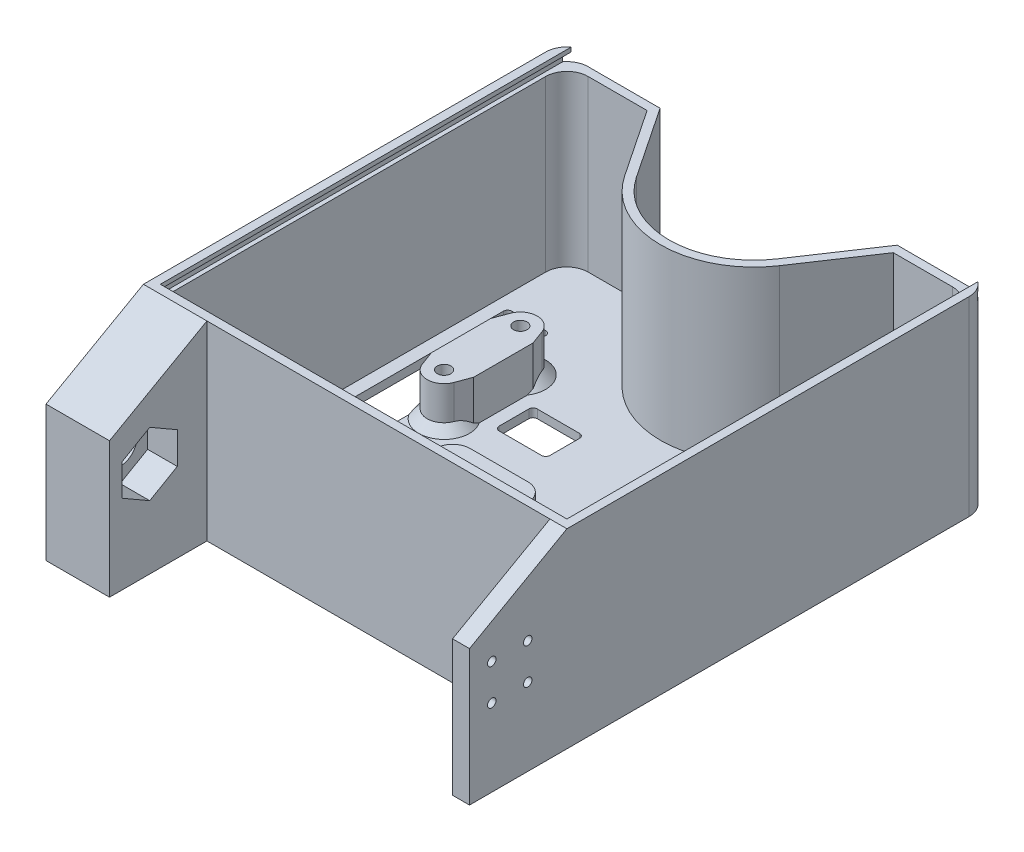
SolidWorks part; units mm, degrees
material "PVC hart"
ref_plane "Ebene vorne" through (0, 0, 0) normal (0, 0, 1) x (1, 0, 0)
ref_plane "Ebene oben" through (0, 0, 0) normal (0, 1, 0) x (1, 0, 0)
ref_plane "Ebene rechts" through (0, 0, 0) normal (1, 0, 0) x (0, 0, -1)
sketch "Grundplatte" plane through (0, 0, 0) normal (0, 1, 0) x (1, 0, 0)
  line L0 (0, 69.0751) -> (0, -94.5087) construction
  line L2 (-50, 50) -> (-50, -50)
  line L3 (-50, -50) -> (50, -50)
  line L4 (50, 50) -> (50, -50)
  line L5 (-50, 50) -> (50, -50) construction
  line L6 (-50, -50) -> (50, 50) construction
  line L7 (-50, 50) -> (-28, 50)
  line L8 (-28, 50) -> (-16.6199, 33)
  line L9 (28, 50) -> (16.6199, 33)
  line L10 (50, 50) -> (28, 50)
  arc A0 (-16.6199, 33) -> (16.6199, 33) centre (0, 44.1257) ccw
  point P0 (0, 0)
  dimension "D4" = 20
  dimension "D1" = 100
  dimension "D2" = 100
  dimension "D3" = 22
  dimension "D5" = 17
extrude "Aufsatz-Linear austragen1" add sketch "Grundplatte" along normal blind 45
shell "Wandung1" thickness 2 removed face at (0, 45, -19.6407)
sketch "Skizze1" plane through (0, 2, 0) normal (0, 1, 0) x (1, 0, 0)
  line L0 (0, 51.8201) -> (0, -55.3816) construction
  line L1 (-28, 50) -> (-50, 50) construction
  line L2 (-45, 31) -> (-35, 31)
  line L3 (-45, 31) -> (-45, -11)
  line L4 (-45, -11) -> (-35, -11)
  line L5 (-35, 31) -> (-35, -11)
  line L6 (-45, 31) -> (-35, -11) construction
  line L7 (-45, -11) -> (-35, 31) construction
  line L8 (50, 50) -> (28, 50) construction
  line L9 (35, 31) -> (45, 31)
  line L10 (35, 31) -> (35, -11)
  line L11 (35, -11) -> (45, -11)
  line L12 (45, 31) -> (45, -11)
  line L13 (35, 31) -> (45, -11) construction
  line L14 (35, -11) -> (45, 31) construction
  point P3 (-40, 10)
  point P10 (40, 10)
  dimension "D1" = 10
  dimension "D2" = 42
  dimension "D3" = 40
  dimension "D4" = 40
  dimension "D5" = 42
  dimension "D6" = 10
  dimension "D7" = 40
  dimension "D8" = 40
extrude "Schnitt-Linear austragen1" cut sketch "Skizze1" against normal up to surface (2 mm away) up to face at (0, 0, -19.6407)
sketch "Skizze2" plane through (0, 2, 0) normal (0, 1, 0) x (1, 0, 0)
  line L20 (-65.457, 10) -> (65.6069, 10) construction
  line L21 (0, 51.8201) -> (0, -54.6693) construction
  line L22 (-35, -11) -> (-35, 31) construction
  line L24 (-35, 16) -> (-35, 4)
  line L26 (-25, 16) -> (-25, 4)
  line L27 (-35, 16) -> (-25, 4) construction
  line L28 (-35, 4) -> (-25, 16) construction
  line L33 (35, 16) -> (35, 17)
  line L34 (33.7533, 20.3831) -> (35, 17)
  line L36 (-35, 16) -> (-35, 17)
  line L37 (-25, 16) -> (-25, 17)
  line L38 (-35, 4) -> (-35, 3)
  line L39 (-25, 4) -> (-25, 3)
  line L40 (-26.2467, 20.3831) -> (-25, 17)
  line L41 (-33.7533, 20.3831) -> (-35, 17)
  line L42 (-26.2467, -0.3831) -> (-25, 3)
  line L43 (-33.7533, -0.3831) -> (-35, 3)
  line L44 (26.2467, 20.3831) -> (25, 17)
  line L45 (25, 16) -> (25, 17)
  line L46 (25, 16) -> (25, 4)
  line L47 (25, 4) -> (25, 3)
  line L48 (26.2467, -0.3831) -> (25, 3)
  line L49 (33.7533, -0.3831) -> (35, 3)
  line L50 (35, 4) -> (35, 3)
  line L51 (35, 16) -> (35, 4)
  circle A4 centre (-30, 19) radius 1.6
  circle A5 centre (-30, 1) radius 1.6
  arc A6 (-26.2467, 20.3831) -> (-33.7533, 20.3831) centre (-30, 19) ccw
  arc A7 (-26.2467, -0.3831) -> (-33.7533, -0.3831) centre (-30, 1) cw
  circle A8 centre (30, 1) radius 1.6
  circle A9 centre (30, 19) radius 1.6
  arc A10 (26.2467, 20.3831) -> (33.7533, 20.3831) centre (30, 19) cw
  arc A11 (26.2467, -0.3831) -> (33.7533, -0.3831) centre (30, 1) ccw
  point P4 (-30, 10)
  point P9 (30, 10)
  dimension "D9" = 3.2
  dimension "D10" = 3.2
  dimension "D13" = 4
  dimension "D14" = 4
  dimension "D2" = 30
  dimension "D3" = 10
  dimension "D5" = 1
  dimension "D6" = 1
  dimension "D7" = 1
  dimension "D8" = 1
  dimension "D11" = 9
  dimension "D12" = 9
extrude "Aufsatz-Linear austragen2" add sketch "Skizze2" along normal blind 10
fillet "Verrundung1" radius 1 8 edges at (35, 1, -31) (45, 1, -31) (35, 1, 11) (45, 1, 11) (-35, 1, 11) (-45, 1, 11) (-45, 1, -31) (-35, 1, -31)
sketch "Skizze6" plane through (0, 12, 0) normal (0, 1, 0) x (1, 0, 0)
  circle A0 centre (-30, 19) radius 1.6
  circle A1 centre (-30, 1) radius 1.6
  circle A2 centre (30, 19) radius 1.6
  circle A3 centre (30, 1) radius 1.6
  dimension "D1" = 3.2
  dimension "D2" = 3.2
  dimension "D3" = 3.2
  dimension "D4" = 3.2
extrude "Schnitt-Linear austragen2" cut sketch "Skizze6" against normal through all
sketch "Skizze7" plane through (0, 0, 0) normal (0, -1, 0) x (1, 0, 0)
  line L0 (0, 58.5427) -> (0, -57.727) construction
  line L1 (-26.7091, -1) -> (-28.3546, 1.85)
  line L2 (-28.3546, 1.85) -> (-31.6454, 1.85)
  line L3 (-31.6454, 1.85) -> (-33.2909, -1)
  line L4 (-33.2909, -1) -> (-31.6454, -3.85)
  line L5 (-31.6454, -3.85) -> (-28.3546, -3.85)
  line L6 (-28.3546, -3.85) -> (-26.7091, -1)
  line L7 (28.3546, -21.85) -> (26.7091, -19)
  line L8 (-26.7091, -19) -> (-28.3546, -16.15)
  line L9 (-28.3546, -16.15) -> (-31.6454, -16.15)
  line L10 (-31.6454, -16.15) -> (-33.2909, -19)
  line L11 (-33.2909, -19) -> (-31.6454, -21.85)
  line L12 (-31.6454, -21.85) -> (-28.3546, -21.85)
  line L13 (-28.3546, -21.85) -> (-26.7091, -19)
  line L14 (31.6454, -21.85) -> (28.3546, -21.85)
  line L15 (33.2909, -19) -> (31.6454, -21.85)
  line L16 (31.6454, -16.15) -> (33.2909, -19)
  line L17 (28.3546, -16.15) -> (31.6454, -16.15)
  line L18 (26.7091, -19) -> (28.3546, -16.15)
  line L19 (28.3546, -3.85) -> (26.7091, -1)
  line L20 (31.6454, -3.85) -> (28.3546, -3.85)
  line L21 (33.2909, -1) -> (31.6454, -3.85)
  line L22 (31.6454, 1.85) -> (33.2909, -1)
  line L23 (28.3546, 1.85) -> (31.6454, 1.85)
  line L24 (26.7091, -1) -> (28.3546, 1.85)
  circle A0 centre (-30, -1) radius 2.85 construction
  circle A1 centre (-30, -19) radius 2.85 construction
  dimension "D1" = 5.7
  dimension "D2" = 5.7
extrude "Schnitt-Linear austragen3" cut sketch "Skizze7" against normal offset from surface (9 mm away) 3 up to face at (30, 12, -2.6)
chamfer "Fase1" distance 2 angle 45 8 edges at (34.3766, 2, -1.3084) (30, 2, 3) (34.3766, 2, -18.6916) (30, 2, -23) (-34.3766, 2, -18.6916) (-30, 2, -23) (-34.3766, 2, -1.3084) (-30, 2, 3)
sketch "Skizze8" plane through (0, 0, 0) normal (0, -1, 0) x (1, 0, 0)
  line L0 (0, 60.6503) -> (0, -60.3099) construction
  line L1 (22, -5) -> (10, -5)
  line L2 (-22, -14) -> (-10, -14)
  line L3 (-22, -14) -> (-22, -5)
  line L4 (-22, -5) -> (-10, -5)
  line L5 (-10, -14) -> (-10, -5)
  line L10 (10, -14) -> (10, -5)
  line L11 (22, -14) -> (10, -14)
  line L12 (22, -14) -> (22, -5)
  circle A0 centre (-30, -1) radius 1.6 construction
  dimension "D2" = 4
  dimension "D1" = 12
  dimension "D3" = 10
  dimension "D4" = 9
extrude "Schnitt-Linear austragen4" cut sketch "Skizze8" against normal up to surface (2 mm away) up to face at (-36.1139, 2, -10)
fillet "Verrundung2" radius 1 8 edges at (-22, 1, -14) (-22, 1, -5) (-10, 1, -5) (-10, 1, -14) (22, 1, -14) (22, 1, -5) (10, 1, -14) (10, 1, -5)
fillet "Verrundung3" radius 5 2 edges at (-50, 22.5, -50) (50, 22.5, -50)
fillet "Verrundung4" radius 5 2 edges at (48, 23.5, -48) (-48, 23.5, -48)
sketch "Skizze9" plane through (0, 0, 0) normal (0, -1, 0) x (1, 0, 0)
  line L0 (0, 55.7734) -> (0, -61.0444) construction
  line L1 (-11, -5) -> (-21, -5) construction
  line L2 (-6.8, 43) -> (6.8, 43)
  line L3 (-8, 41.8) -> (-8, 20.2)
  line L4 (-6.8, 19) -> (6.8, 19)
  line L5 (8, 41.8) -> (8, 20.2)
  line L6 (-8, 43) -> (8, 19) construction
  line L7 (-8, 19) -> (8, 43) construction
  arc A0 (6.8, 19) -> (8, 20.2) centre (6.8, 20.2) ccw
  arc A1 (-8, 20.2) -> (-6.8, 19) centre (-6.8, 20.2) ccw
  arc A2 (-6.8, 43) -> (-8, 41.8) centre (-6.8, 41.8) ccw
  arc A3 (6.8, 43) -> (8, 41.8) centre (6.8, 41.8) cw
  point P3 (0, 31)
  dimension "D4" = 1.2
  dimension "D1" = 24
  dimension "D2" = 16
  dimension "D3" = 36
extrude "Schnitt-Linear austragen5" cut sketch "Skizze9" against normal up to next
sketch "Skizze11" plane through (0, 2, 0) normal (0, 1, 0) x (1, 0, 0)
  line L25 (-6.8, -46) -> (6.8, -46)
  line L26 (-11, -20.2) -> (-11, -41.8)
  line L27 (11, -41.8) -> (11, -20.2)
  line L28 (6.8, -16) -> (-6.8, -16)
  line L29 (-6.8, -46) -> (6.8, -46)
  line L30 (-11, -20.2) -> (-11, -41.8)
  line L31 (11, -41.8) -> (11, -20.2)
  line L32 (6.8, -16) -> (-6.8, -16)
  line L62 (-8, -20.2) -> (-8, -41.8)
  line L63 (-6.8, -43) -> (6.8, -43)
  line L64 (8, -41.8) -> (8, -20.2)
  line L65 (-6.8, -19) -> (6.8, -19)
  arc A19 (6.8, -46) -> (11, -41.8) centre (6.8, -41.8) ccw
  arc A20 (-11, -41.8) -> (-6.8, -46) centre (-6.8, -41.8) ccw
  arc A21 (-6.8, -16) -> (-11, -20.2) centre (-6.8, -20.2) ccw
  arc A22 (11, -20.2) -> (6.8, -16) centre (6.8, -20.2) ccw
  arc A23 (6.8, -46) -> (11, -41.8) centre (6.8, -41.8) ccw
  arc A24 (-11, -41.8) -> (-6.8, -46) centre (-6.8, -41.8) ccw
  arc A25 (-6.8, -16) -> (-11, -20.2) centre (-6.8, -20.2) ccw
  arc A26 (11, -20.2) -> (6.8, -16) centre (6.8, -20.2) ccw
  arc A50 (-6.8, -19) -> (-8, -20.2) centre (-6.8, -20.2) ccw
  arc A51 (6.8, -19) -> (8, -20.2) centre (6.8, -20.2) cw
  arc A52 (-6.8, -43) -> (-8, -41.8) centre (-6.8, -41.8) cw
  arc A53 (6.8, -43) -> (8, -41.8) centre (6.8, -41.8) ccw
  dimension "D1" = 3
extrude "Aufsatz-Linear austragen3" add sketch "Skizze11" along normal blind 12
sketch "Skizze12" plane through (0, 14, 0) normal (0, 1, 0) x (1, 0, 0)
  line L30 (11, -41.8) -> (11, -20.2)
  line L31 (-6.8, -46) -> (6.8, -46)
  line L32 (-11, -20.2) -> (-11, -41.8)
  line L33 (6.8, -16) -> (-6.8, -16)
  line L34 (11, -41.8) -> (11, -20.2)
  line L35 (-6.8, -46) -> (6.8, -46)
  line L36 (-11, -20.2) -> (-11, -41.8)
  line L37 (6.8, -16) -> (-6.8, -16)
  arc A14 (6.8, -46) -> (11, -41.8) centre (6.8, -41.8) ccw
  arc A15 (-11, -41.8) -> (-6.8, -46) centre (-6.8, -41.8) ccw
  arc A16 (-6.8, -16) -> (-11, -20.2) centre (-6.8, -20.2) ccw
  arc A17 (11, -20.2) -> (6.8, -16) centre (6.8, -20.2) ccw
  arc A18 (6.8, -46) -> (11, -41.8) centre (6.8, -41.8) ccw
  arc A19 (-11, -41.8) -> (-6.8, -46) centre (-6.8, -41.8) ccw
  arc A20 (-6.8, -16) -> (-11, -20.2) centre (-6.8, -20.2) ccw
  arc A21 (11, -20.2) -> (6.8, -16) centre (6.8, -20.2) ccw
  dimension "D1" = 3
extrude "Aufsatz-Linear austragen4" add sketch "Skizze12" along normal blind 2
chamfer "Fase2" distance 2 angle 45 8 edges at (-11, 2, 31) (-9.7698, 2, 44.7698) (-9.7698, 2, 17.2302) (0, 2, 46) (0, 2, 16) (9.7698, 2, 44.7698) (9.7698, 2, 17.2302) (11, 2, 31)
sketch "Skizze13" plane through (0, 16, 0) normal (0, 1, 0) x (1, 0, 0)
  line L0 (0, 40.7845) -> (0, -65.4996) construction
  line L1 (-15.9895, -31) -> (16.789, -31) construction
  line L2 (6.8, -16) -> (-6.8, -16) construction
  line L3 (-6.8, -46) -> (6.8, -46) construction
  circle A0 centre (0, -23) radius 1.6
  circle A1 centre (0, -39) radius 1.6
  dimension "D1" = 3.2
  dimension "D2" = 3.2
  dimension "D3" = 16
extrude "Schnitt-Linear austragen6" cut sketch "Skizze13" along direction (0, 1, 0) on the side against the normal up to surface (2 mm away) up to face at (0, 14, 31)
sketch "Skizze14" plane through (0, 0, 50) normal (0, 0, 1) x (1, 0, 0)
  line L0 (0, 49.837) -> (0, -24.1023) construction
  line L1 (-50, 45) -> (-50, 0)
  line L2 (-50, 0) -> (-35, 0)
  line L3 (-50, 0) -> (50, 0) construction
  line L4 (-35, 0) -> (-35, 45)
  line L5 (-50, 45) -> (50, 45) construction
  line L6 (-35, 45) -> (-50, 45)
  line L7 (50, 45) -> (46, 45)
  line L8 (46, 45) -> (46, 0)
  line L9 (46, 0) -> (50, 0)
  line L10 (50, 0) -> (50, 45)
  dimension "D1" = 15
  dimension "D2" = 4
extrude "Aufsatz-Linear austragen5" add sketch "Skizze14" along normal blind 23
sketch "Skizze18" plane through (50, 0, 0) normal (1, 0, 0) x (0, 0, -1)
  line L0 (-50, 46.4423) -> (-50, -7.8316) construction
  line L1 (-73, 0) -> (-73, 45) construction
  line L3 (-73, 0) -> (45, 0) construction
  circle A0 centre (-63.5, 22.5) radius 6 construction
  circle A5 centre (-59.2574, 18.2574) radius 1
  circle A9 centre (-67.7426, 18.2574) radius 1
  circle A11 centre (-67.7426, 26.7426) radius 1
  circle A13 centre (-59.2574, 26.7426) radius 1
  point P27 (-63.5, 22.5)
  point P28 (-63.5, 22.5)
  dimension "D2" = 12
  dimension "D5" = 2
  dimension "D6" = 2
  dimension "D7" = 2
  dimension "D8" = 2
  dimension "D1" = 23
  dimension "D3" = 13.5
  dimension "D4" = 22.5
extrude "Schnitt-Linear austragen8" cut sketch "Skizze18" against normal up to surface (4 mm away) up to face at (46, 22.5, 61.5)
sketch "Skizze19" plane through (46, 0, 0) normal (-1, 0, 0) x (0, 0, 1)
  line L0 (50, 40.9842) -> (50, -6.1788) construction
  line L1 (73, 45) -> (73, 0) construction
  line L2 (73, 45) -> (50, 45) construction
  circle A0 centre (63.5, 22.5) radius 2.5
  dimension "D2" = 5
  dimension "D1" = 23
  dimension "D3" = 13.5
  dimension "D4" = 22.5
extrude "Schnitt-Linear austragen9" cut sketch "Skizze19" against normal blind 2.5
sketch "Skizze20" plane through (0, 0, 50) normal (0, 0, 1) x (1, 0, 0)
  line L0 (46, 45) -> (46, 0) construction
  line L1 (41, 27.5) -> (46, 27.5)
  line L2 (41, 27.5) -> (41, 17.5)
  line L3 (41, 17.5) -> (46, 17.5)
  line L4 (46, 27.5) -> (46, 17.5)
  line L5 (41, 27.5) -> (46, 17.5) construction
  line L6 (41, 17.5) -> (46, 27.5) construction
  line L7 (-35, 45) -> (46, 45) construction
  point P0 (43.5, 22.5)
  dimension "D1" = 10
  dimension "D2" = 5
  dimension "D3" = 22.5
extrude "Schnitt-Linear austragen10" cut sketch "Skizze20" against normal up to surface (2 mm away) up to face at (0, 16.3333, 48)
sketch "Skizze21" plane through (-50, 0, 0) normal (-1, 0, 0) x (0, 0, 1)
  line L0 (50, 45.8781) -> (50, -12.9091) construction
  line L1 (73, 45) -> (73, 0) construction
  line L2 (-45, 45) -> (73, 45) construction
  circle A0 centre (63.5, 22.5) radius 4
  dimension "D4" = 8
  dimension "D1" = 23
  dimension "D2" = 13.5
  dimension "D3" = 22.5
extrude "Schnitt-Linear austragen11" cut sketch "Skizze21" against normal up to surface (15 mm away) contours A0 up to face at (-35, 22.5, 61.5)
sketch "Skizze23" plane through (-50, 0, 0) normal (-1, 0, 0) x (0, 0, 1)
  circle A0 centre (63.5, 22.5) radius 7.5
  dimension "D1" = 15
extrude "Schnitt-Linear austragen12" cut sketch "Skizze23" against normal blind 1
sketch "Skizze24" plane through (-49, 0, 0) normal (-1, 0, 0) x (0, 0, 1)
  circle A0 centre (63.5, 22.5) radius 7.5
  dimension "D1" = 15
extrude "Schnitt-Linear austragen13" cut sketch "Skizze24" against normal blind 4 draft 45
sketch "Skizze26" plane through (-35, 0, 0) normal (1, 0, 0) x (0, 0, -1)
  line L0 (-73, 0) -> (-73, 45) construction
  line L1 (-57, 18.7472) -> (-57, 26.2528)
  line L2 (-57, 26.2528) -> (-63.5, 30.0056)
  line L3 (-63.5, 30.0056) -> (-70, 26.2528)
  line L4 (-70, 26.2528) -> (-70, 18.7472)
  line L5 (-70, 18.7472) -> (-63.5, 14.9944)
  line L6 (-63.5, 14.9944) -> (-57, 18.7472)
  circle A0 centre (-63.5, 22.5) radius 6.5 construction
  dimension "D1" = 13
extrude "Schnitt-Linear austragen14" cut sketch "Skizze26" against normal blind 7
sketch "Skizze29" plane through (-50, 0, 0) normal (-1, 0, 0) x (0, 0, 1)
  line L0 (50, 50.1212) -> (50, -3.8482) construction
  line L1 (73, 45) -> (73, 0) construction
  line L2 (73, 45) -> (73, 32)
  line L3 (73, 32) -> (50, 45)
  line L4 (50, 45) -> (73, 45)
  point P7 (50, 50.1212)
  dimension "D1" = 23
  dimension "D2" = 13
extrude "Schnitt-Linear austragen15" cut sketch "Skizze29" against normal up to surface (100 mm away) up to face at (50, 26.7426, 58.2574)
sketch "Skizze31" plane through (0, 0, -50) normal (0, 0, -1) x (-1, 0, 0)
  line L0 (-48, 45) -> (-48, 42)
  line L1 (-45, 45) -> (-50, 45) construction
  line L2 (-48, 42) -> (48, 42)
  line L3 (48, 42) -> (48, 45)
  line L4 (50, 45) -> (45, 45) construction
  line L5 (48, 45) -> (-48, 45)
  line L6 (-50, 0) -> (-50, 45) construction
  line L7 (50, 45) -> (50, 0) construction
  dimension "D1" = 2
  dimension "D2" = 2
  dimension "D3" = 3
extrude "Schnitt-Linear austragen16" cut sketch "Skizze31" against normal blind 30
sketch "Skizze32" plane through (0, 0, -50) normal (0, 0, -1) x (-1, 0, 0)
  line L0 (-48, 45) -> (-50, 45) construction
  line L2 (-49, 44) -> (-49, 42)
  line L3 (-49, 42) -> (49, 42)
  line L4 (49, 42) -> (49, 44)
  line L5 (49, 44) -> (-49, 44)
  line L6 (-50, 0) -> (-50, 45) construction
  line L7 (50, 45) -> (50, 0) construction
  dimension "D1" = 1
  dimension "D2" = 3
  dimension "D3" = 1
  dimension "D4" = 1
extrude "Schnitt-Linear austragen17" cut sketch "Skizze32" against normal blind 99
